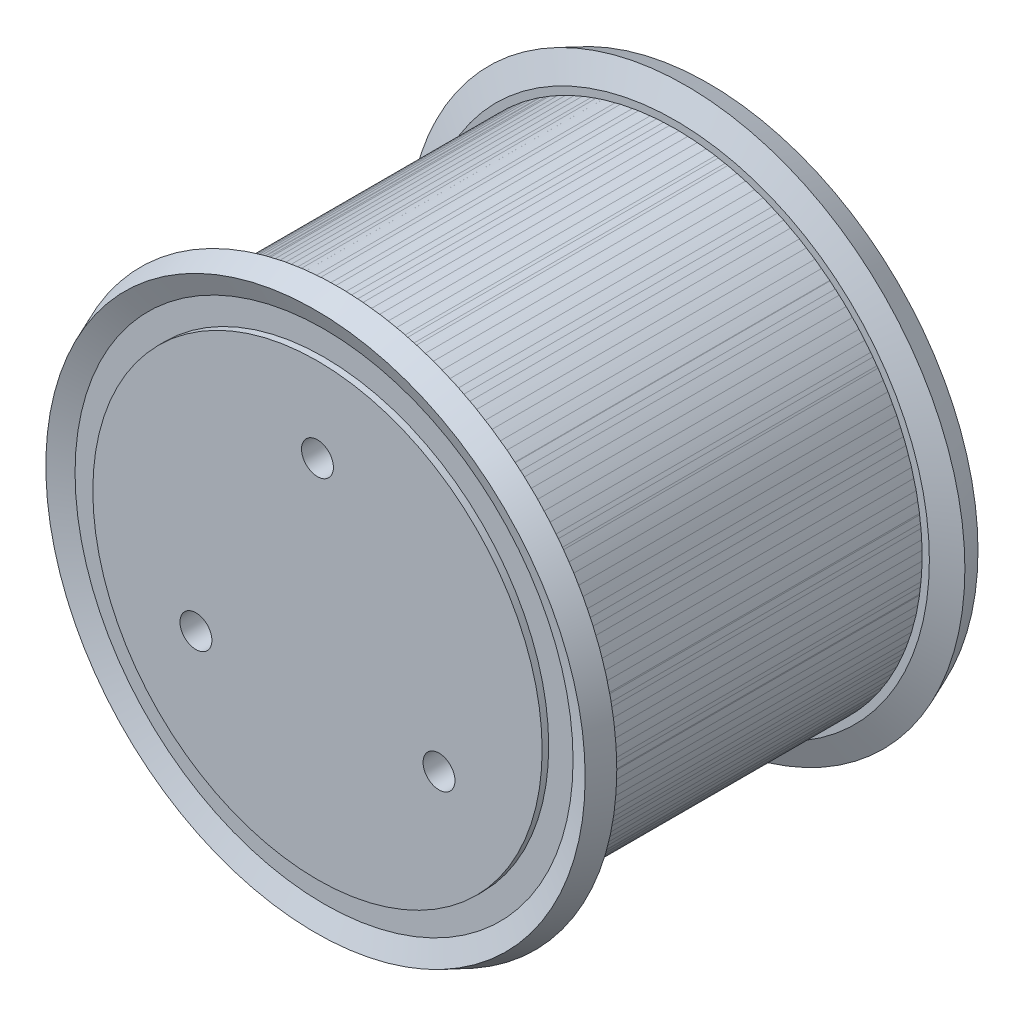
SolidWorks part; units mm, degrees
ref_plane "前视基准面" through (0, 0, 0) normal (0, 0, 1) x (1, 0, 0)
ref_plane "上视基准面" through (0, 0, 0) normal (0, 1, 0) x (1, 0, 0)
ref_plane "右视基准面" through (0, 0, 0) normal (1, 0, 0) x (0, 0, -1)
ref_axis "基准轴1" through (0, 0, 55) along (0, 0, -1)
sketch "SketchRevolveGearBelt01" plane through (0, 0, 0) normal (1, 0, 0) x (0, 0, -1)
  line L0 (0, 0) -> (1, 0) construction
  line L1 (15.24, 0) -> (15.24, 17.6084)
  line L2 (15.24, 17.6084) -> (14.7244, 17.6084)
  line L3 (14.7244, 17.6084) -> (14.7244, 19.5169)
  line L4 (14.7244, 19.5169) -> (15.3953, 21.1368)
  line L5 (15.3953, 21.1368) -> (13.6424, 21.8629)
  line L6 (13.6424, 21.8629) -> (12.827, 19.8944)
  line L7 (12.827, 19.8944) -> (12.827, 19.3229)
  line L8 (12.827, 19.3229) -> (-12.827, 19.3229)
  line L9 (-12.827, 19.3229) -> (-12.827, 19.8944)
  line L10 (-12.827, 19.8944) -> (-13.6424, 21.8629)
  line L11 (-13.6424, 21.8629) -> (-15.3953, 21.1368)
  line L12 (-15.3953, 21.1368) -> (-14.7244, 19.5169)
  line L13 (-14.7244, 19.5169) -> (-14.7244, 17.6084)
  line L14 (-14.7244, 17.6084) -> (-15.24, 17.6084)
  line L15 (-15.24, 17.6084) -> (-15.24, 0)
  line L16 (-15.24, 0) -> (15.24, 0)
  dimension "GearBeltFlange1OutsideLength" = 1.9086
  dimension "GearBeltFlange1X" = 0.6709
  dimension "GearBeltFlange1Y" = 1.6198
  dimension "GearBeltFlangeThickness" = 1.8974
  dimension "GearBeltFlangeInside" = 0.5715
  dimension "GearBeltOutsideDiameter" = 19.3229
  dimension "GearBeltFlange2X" = 0.6709
revolve "GearBelt01" add sketch "SketchRevolveGearBelt01" angle 360 about L0
sketch "SketchToothGearBelt01" plane through (0, 0, 0) normal (0, 0, 1) x (1, 0, 0)
  arc A0 (19.2019, 2.1549) -> (19.2019, -2.1549) centre (0, 0) cw
  spline S0 degree 3 poles (19.2019, -2.1549) (19.2051, -2.1266) (19.2062, -2.0838) (19.2007, -2.0271) (19.1929, -1.985) (19.1817, -1.9438) (19.167, -1.9037) (19.149, -1.8649) (19.1278, -1.8278) (19.1036, -1.7926) (19.0765, -1.7596) (19.0468, -1.7289) (19.0145, -1.7009) (18.9801, -1.6756) (18.9436, -1.6534) (18.9054, -1.6342) (18.8657, -1.6184) (18.8248, -1.6059) (18.7831, -1.597) (18.7407, -1.5914) (18.6735, -1.5892) (18.5873, -1.5911) (18.4822, -1.5873) (18.3832, -1.5753) (18.2854, -1.5557) (18.1895, -1.5285) (18.096, -1.4939) (18.0055, -1.452) (17.9186, -1.4032) (17.8357, -1.3477) (17.7575, -1.2859) (17.6843, -1.2181) (17.6167, -1.1449) (17.5551, -1.0665) (17.4997, -0.9836) (17.4511, -0.8965) (17.4094, -0.806) (17.3749, -0.7124) (17.3478, -0.6164) (17.3285, -0.5186) (17.3165, -0.4196) (17.313, -0.2999) (17.3145, -0.16) (17.3139, 0) (17.3145, 0.16) (17.313, 0.2999) (17.3165, 0.4196) (17.3285, 0.5186) (17.3478, 0.6164) (17.3749, 0.7124) (17.4094, 0.806) (17.4511, 0.8965) (17.4997, 0.9836) (17.5551, 1.0665) (17.6167, 1.1449) (17.6843, 1.2181) (17.7575, 1.2859) (17.8357, 1.3477) (17.9186, 1.4032) (18.0055, 1.452) (18.096, 1.4939) (18.1895, 1.5285) (18.2854, 1.5557) (18.3832, 1.5753) (18.4822, 1.5873) (18.5873, 1.5911) (18.6735, 1.5892) (18.7407, 1.5914) (18.7831, 1.597) (18.8248, 1.6059) (18.8657, 1.6184) (18.9054, 1.6342) (18.9436, 1.6534) (18.9801, 1.6756) (19.0145, 1.7009) (19.0468, 1.7289) (19.0765, 1.7596) (19.1036, 1.7926) (19.1278, 1.8278) (19.149, 1.8649) (19.167, 1.9037) (19.1817, 1.9438) (19.1929, 1.985) (19.2007, 2.0271) (19.2062, 2.0838) (19.2051, 2.1266) (19.2019, 2.1549) knots 0 0 0 0 0.013004 0.019506 0.026009 0.032511 0.039013 0.045515 0.052017 0.058519 0.065021 0.071524 0.078026 0.084528 0.09103 0.097532 0.104034 0.110536 0.117038 0.123541 0.130043 0.147745 0.16292 0.178095 0.19327 0.208445 0.223621 0.238796 0.253971 0.269146 0.284321 0.299496 0.314671 0.329846 0.345021 0.360196 0.375371 0.390546 0.405721 0.420897 0.436072 0.451247 0.475623 0.5 0.524377 0.548753 0.563928 0.579103 0.594279 0.609454 0.624629 0.639804 0.654979 0.670154 0.685329 0.700504 0.715679 0.730854 0.746029 0.761204 0.776379 0.791555 0.80673 0.821905 0.83708 0.852255 0.869957 0.876459 0.882962 0.889464 0.895966 0.902468 0.90897 0.915472 0.921974 0.928476 0.934979 0.941481 0.947983 0.954485 0.960987 0.967489 0.973991 0.980494 0.986996 1 1 1 1
extrude "ToothExtrudeCutGearBelt01" cut sketch "SketchToothGearBelt01" against normal blind 12.827 and the other way blind 12.827
pattern_circular "PatternGearBelt01" count 25 over 360 about axis through (0, 0, 55) along (0, 0, -1) of "ToothExtrudeCutGearBelt01"
sketch "草图5" plane through (0, 0, -15.24) normal (0, 0, -1) x (-1, 0, 0)
  circle A0 centre (0, 0) radius 11 construction
  circle A1 centre (0, 11) radius 1.5
  circle A4 centre (9.5263, -5.5) radius 1.5
  circle A5 centre (-9.5263, -5.5) radius 1.5
  point P8 (-0.7219, 3.3021)
  point P11 (0, 0)
  dimension "D1" = 22
  dimension "D2" = 3
  dimension "D3" = 3
hole_wizard "M3 螺纹孔1" positions "3D草图1" profile "草图6" tap size "M3" standard "GB"
sketch3d "3D草图1"
  point P0 (9.5263, -5.5, -15.24)
  point P3 (0, 11, -15.24)
  point P6 (-9.5263, -5.5, -15.24)
cosmetic thread "孔螺蚊线1" parameters "D1"=7, "D2"=3
cosmetic thread "孔螺蚊线2" parameters "D1"=7, "D2"=3
cosmetic thread "孔螺蚊线3" parameters "D1"=7, "D2"=3
sketch "草图6" plane through (9.5263, -5.5, -15.24) normal (1, 0, 0) x (0, 1, 0)
  line L0 (0, 0) -> (0, 8.7511)
  line L1 (0, 8.7511) -> (1.25, 8)
  line L2 (1.25, 8) -> (1.25, 0)
  line L5 (1.25, 0) -> (0, 0)
  line L10 (0, 8.7511) -> (-1.25, 8) construction
  line L11 (0, -6.35) -> (0, 107.95) construction
  dimension "螺纹孔钻头直径" = 2.5
  dimension "螺纹孔钻头深度" = 8
  dimension "导头角度" = 118
mirror "镜向1" about plane through (0, 0, 0) normal (0, 0, 1) of "M3 螺纹孔1"
